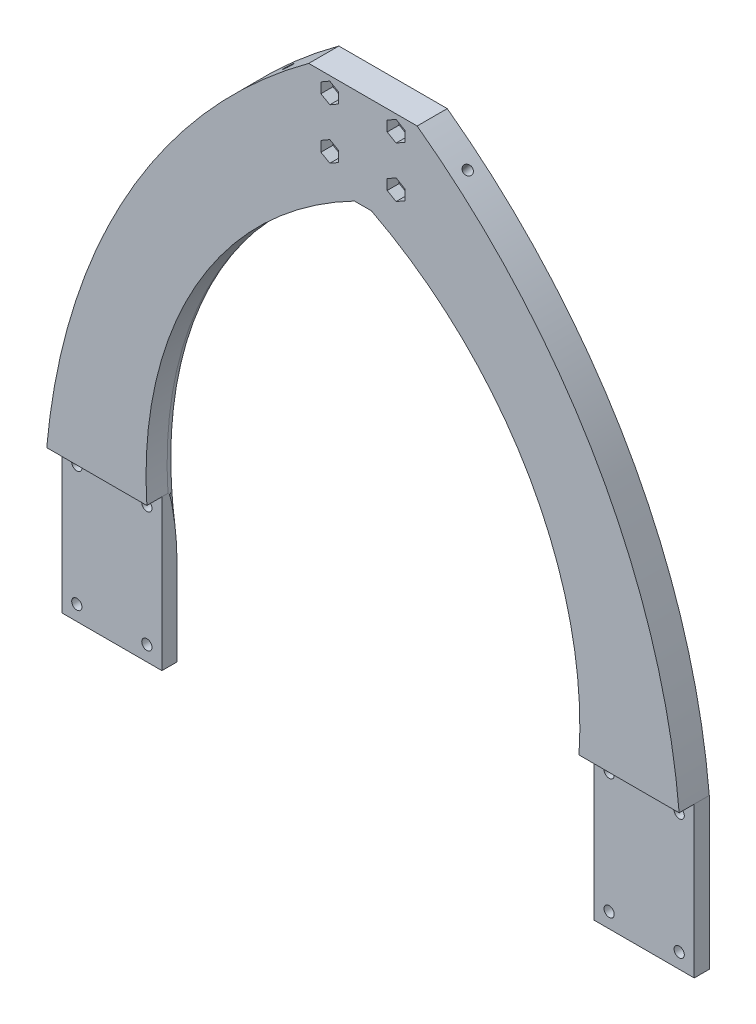
SolidWorks part; units mm, degrees
ref_plane "Ebene vorne" through (0, 0, 0) normal (0, 0, 1) x (1, 0, 0)
ref_plane "Ebene oben" through (0, 0, 0) normal (0, 1, 0) x (1, 0, 0)
ref_plane "Ebene rechts" through (0, 0, 0) normal (1, 0, 0) x (0, 0, -1)
sketch "Skizze1" plane through (0, 0, 0) normal (0, 1, 0) x (1, 0, 0)
  line L1 (-105, -210) -> (105, -210)
  line L2 (-105, -210) -> (-105, 210)
  line L3 (-105, 210) -> (105, 210)
  line L4 (105, -210) -> (105, 210)
  line L5 (-105, -210) -> (105, 210) construction
  line L6 (-105, 210) -> (105, -210) construction
  point P0 (0, 0)
  dimension "D1" = 210
  dimension "D2" = 420
extrude "Aufsatz-Linear austragen1" add sketch "Skizze1" along normal blind 10
ref_plane "Ebene1" through (0, -97.5366, 81.8429) normal (0, -0.766, 0.6428) x (1, 0, 0)
sketch "Skizze2" plane through (0, -97.5366, 81.8429) normal (0, -0.766, 0.6428) x (1, 0, 0)
  line L1 (-105, 167.2972) -> (105, 167.2972) construction
  circle A0 centre (0, 147.2972) radius 5
  dimension "D1" = 10
  dimension "D2" = 20
extrude "Schnitt-Linear austragen1" [suppressed] cut sketch "Skizze2" against normal blind 30 and the other way blind 10
sketch "Skizze3" [suppressed] plane through (0, -67.9923, 57.0523) normal (0, -0.766, 0.6428) x (1, 0, 0)
  circle A0 centre (0, 101.3345) radius 5
  dimension "D1" = 10
extrude "Aufsatz-Linear austragen2" [suppressed] add sketch "Skizze3" along normal blind 0.1
sketch "Skizze4" plane through (0, -97.5366, 81.8429) normal (0, -0.766, 0.6428) x (1, 0, 0)
  line L0 (0, 167.2972) -> (0, 159.9002) construction
  line L1 (-105, 167.2972) -> (105, 167.2972) construction
  line L2 (-25, 167.2972) -> (-25, 202.2972)
  line L3 (-25, 202.2972) -> (25, 202.2972)
  line L4 (-25, 167.2972) -> (25, 167.2972)
  line L5 (25, 167.2972) -> (25, 202.2972)
  point P10 (0, 202.2972)
  dimension "D1" = 50
  dimension "D2" = 35
extrude "Aufsatz-Linear austragen3" [suppressed] add sketch "Skizze4" against normal blind 10 separate body
sketch "Skizze5" plane through (0, 10, 0) normal (0, 1, 0) x (1, 0, 0)
  line L0 (0, 0) -> (0, -210) construction
  line L1 (-105, -210) -> (105, -210) construction
  line L2 (105, -210) -> (18, -210)
  line L3 (-18, -210) -> (-105, -56)
  line L4 (-105, 210) -> (-105, -210) construction
  line L5 (-105, -56) -> (-105, -210)
  line L6 (-105, -210) -> (-18, -210)
  line L7 (105, -56) -> (105, -210)
  line L8 (18, -210) -> (105, -56)
  line L9 (-105, 210) -> (-105, 125)
  line L10 (-105, 125) -> (105, 125)
  line L11 (105, -210) -> (105, 210) construction
  line L12 (105, 125) -> (105, 210)
  line L13 (105, 210) -> (-105, 210)
  line L14 (71.7468, -56) -> (-71.7468, -56)
  line L15 (-71.7468, -56) -> (-2.8247, -178)
  line L16 (71.7468, -56) -> (2.8247, -178)
  line L17 (-2.8247, -178) -> (2.8247, -178)
  line L18 (2.8247, -178) -> (0, -183) construction
  line L19 (-2.8247, -178) -> (0, -183) construction
  point P27 (0, -56)
  dimension "D1" = 36
  dimension "D2" = 154
  dimension "D3" = 85
  dimension "D4" = 32
  dimension "D5" = 27
extrude "Schnitt-Linear austragen2" cut sketch "Skizze5" against normal blind 10
sketch "Skizze6" plane through (0, 10, 0) normal (0, 1, 0) x (1, 0, 0)
  line L0 (0, -210) -> (0, -178) construction
  line L1 (-18, -210) -> (18, -210) construction
  line L2 (-2.8247, -178) -> (2.8247, -178) construction
  line L3 (0, -196.59) -> (-21.075, -196.59) construction
  circle A0 centre (-11, -205) radius 1.7
  circle A1 centre (-11, -188.18) radius 1.7
  circle A2 centre (11, -205) radius 1.7
  circle A3 centre (11, -188.18) radius 1.7
  dimension "D1" = 3.4
  dimension "D2" = 11
  dimension "D3" = 5
  dimension "D4" = 13.41
extrude "Schnitt-Linear austragen3" cut sketch "Skizze6" against normal through all
sketch "Skizze7" plane through (0, 0, 0) normal (0, -1, 0) x (1, 0, 0)
  line L0 (-11, 205) -> (-11, 210) construction
  line L1 (-18, 210) -> (18, 210) construction
  line L2 (-11, 205) -> (-5.1092, 205) construction
  line L3 (-11, 208.4064) -> (-8.05, 206.7032)
  line L4 (-8.05, 206.7032) -> (-8.05, 203.2968)
  line L5 (-11, 201.5936) -> (-8.05, 203.2968)
  line L6 (-11, 201.5936) -> (-13.95, 203.2968)
  line L7 (-13.95, 206.7032) -> (-13.95, 203.2968)
  line L8 (-11, 208.4064) -> (-13.95, 206.7032)
  line L9 (0, 210) -> (0, 121.6034) construction
  line L10 (11, 205) -> (11, 188.18) construction
  line L11 (11, 196.59) -> (0, 196.59) construction
  line L12 (11, 208.4064) -> (8.05, 206.7032)
  line L13 (11, 201.5936) -> (8.05, 203.2968)
  line L14 (8.05, 206.7032) -> (8.05, 203.2968)
  line L15 (11, 201.5936) -> (13.95, 203.2968)
  line L16 (13.95, 206.7032) -> (13.95, 203.2968)
  line L17 (11, 208.4064) -> (13.95, 206.7032)
  line L18 (-8.05, 186.4768) -> (-8.05, 189.8832)
  line L19 (-11, 191.5864) -> (-13.95, 189.8832)
  line L20 (-11, 191.5864) -> (-8.05, 189.8832)
  line L21 (-13.95, 186.4768) -> (-13.95, 189.8832)
  line L22 (-11, 184.7736) -> (-13.95, 186.4768)
  line L23 (-11, 184.7736) -> (-8.05, 186.4768)
  line L24 (8.05, 186.4768) -> (8.05, 189.8832)
  line L25 (11, 191.5864) -> (8.05, 189.8832)
  line L26 (11, 191.5864) -> (13.95, 189.8832)
  line L27 (13.95, 186.4768) -> (13.95, 189.8832)
  line L28 (11, 184.7736) -> (13.95, 186.4768)
  line L29 (11, 184.7736) -> (8.05, 186.4768)
  point P10 (-8.05, 205)
  dimension "D1" = 120
  dimension "D2" = 5.9
extrude "Schnitt-Linear austragen4" cut sketch "Skizze7" against normal blind 4
sketch "Skizze8" plane through (0, 10, 0) normal (0, 1, 0) x (1, 0, 0)
  line L0 (105, 115.41) -> (78.872, 115.41) construction
  line L1 (105, -56) -> (105, 125) construction
  line L2 (-105, 125) -> (105, 125) construction
  dimension "D1" = 9.59
ref_plane "Ebene2" through (0, 62.6966, -52.6087) normal (0, 0.766, -0.6428) x (-1, 0, 0)
sketch "Skizze9" plane through (0, 62.6966, -52.6087) normal (0, 0.766, -0.6428) x (-1, 0, 0)
  line L0 (-105, -81.9813) -> (-78.872, -81.9813) construction
  line L1 (-105, 49.3264) -> (-105, -89.3277) construction
  line L2 (0, -45.2589) -> (0, -16.2619) construction
  circle A0 centre (-100, -81.9813) radius 1.7
  circle A1 centre (100, -81.9813) radius 1.7
  circle A2 centre (-30, -81.9813) radius 1.7
  circle A3 centre (30, -81.9813) radius 1.7
  dimension "D1" = 3.4
  dimension "D2" = 5
  dimension "D3" = 30
extrude "Schnitt-Linear austragen5" [suppressed] cut sketch "Skizze9" against normal through all and the other way through all
ref_plane "Ebene3" through (0, 55.0361, -46.1808) normal (0, 0.766, -0.6428) x (-1, 0, 0)
sketch "Skizze10" [suppressed] plane through (0, 55.0361, -46.1808) normal (0, 0.766, -0.6428) x (-1, 0, 0)
  line L0 (-95, -81.9813) -> (-100, -81.9813) construction
  line L1 (-95, -81.9813) -> (-95, -30.0694) construction
  line L2 (-95, -78.7482) -> (-97.8, -80.3647)
  line L3 (-97.8, -80.3647) -> (-97.8, -83.5979)
  line L4 (-95, -85.2145) -> (-97.8, -83.5979)
  line L5 (-95, -85.2145) -> (-92.2, -83.5979)
  line L6 (-92.2, -80.3647) -> (-92.2, -83.5979)
  line L7 (-95, -78.7482) -> (-92.2, -80.3647)
  line L8 (0, 0) -> (0, -45.6283) construction
  line L9 (-30, -81.9813) -> (-95, -81.9813) construction
  line L10 (-62.5, -81.9813) -> (-62.5, -23.1343) construction
  line L11 (-32.8, -80.3647) -> (-32.8, -83.5979)
  line L12 (-30, -85.2145) -> (-32.8, -83.5979)
  line L13 (-30, -85.2145) -> (-27.2, -83.5979)
  line L14 (-27.2, -80.3647) -> (-27.2, -83.5979)
  line L15 (-30, -78.7482) -> (-27.2, -80.3647)
  line L16 (-30, -78.7482) -> (-32.8, -80.3647)
  line L17 (95, -78.7482) -> (92.2, -80.3647)
  line L18 (92.2, -80.3647) -> (92.2, -83.5979)
  line L19 (95, -85.2145) -> (92.2, -83.5979)
  line L20 (95, -85.2145) -> (97.8, -83.5979)
  line L21 (97.8, -80.3647) -> (97.8, -83.5979)
  line L22 (95, -78.7482) -> (97.8, -80.3647)
  line L23 (30, -78.7482) -> (32.8, -80.3647)
  line L24 (30, -78.7482) -> (27.2, -80.3647)
  line L25 (27.2, -80.3647) -> (27.2, -83.5979)
  line L26 (30, -85.2145) -> (27.2, -83.5979)
  line L27 (30, -85.2145) -> (32.8, -83.5979)
  line L28 (32.8, -80.3647) -> (32.8, -83.5979)
  point P9 (-97.8, -81.9813)
  point P31 (97.8, -81.9813)
  dimension "D1" = 120
  dimension "D2" = 5.6
extrude "Schnitt-Linear austragen6" [suppressed] cut sketch "Skizze10" against normal blind 10 and the other way blind 5
sketch "Skizze13" plane through (0, 10, 0) normal (0, 1, 0) x (1, 0, 0)
  line L0 (71.7468, -56) -> (105, -56) construction
  line L1 (71.7468, -56) -> (96.9548, -70.2409) construction
  line L2 (105, -56) -> (18, -210) construction
  line L3 (0, 0) -> (0, -38.1435) construction
  line L4 (2.8247, -178) -> (71.7468, -56) construction
  line L5 (84.3508, -63.1205) -> (108.762, -19.9098) construction
  line L6 (105, -56) -> (105, 125) construction
  line L7 (88.3734, -56) -> (88.3734, -1) construction
  line L8 (99, -58.9512) -> (105.7595, -46.9862) construction
  line L9 (87.7845, -86.4734) -> (62.5765, -72.2325) construction
  line L10 (77.1638, -80.4734) -> (91.1741, -80.4734) construction
  circle A0 centre (99, -58.9512) radius 1.7
  circle A1 centre (76.9708, -58.9512) radius 1.7
  circle A2 centre (86.8414, -80.4734) radius 1.7
  circle A3 centre (-86.8414, -80.4734) radius 1.7
  circle A4 centre (-99, -58.9512) radius 1.7
  circle A5 centre (-76.9708, -58.9512) radius 1.7
  dimension "D1" = 6
  dimension "D5" = 35
  dimension "D3" = 3.4
  dimension "D6" = 3.4
  dimension "D2" = 6
  dimension "D4" = 6
extrude "Schnitt-Linear austragen7" [suppressed] cut sketch "Skizze13" against normal through all
sketch "Skizze14" plane through (103.579, 0, 58.5154) normal (0.8707, 0, 0.4919) x (0.4919, 0, -0.8707)
  line L0 (-32.111, 5) -> (-32.111, 10)
  line L5 (2.889, 0) -> (2.889, 10) construction
  line L6 (-32.111, 5) -> (2.889, 5)
  line L7 (2.889, 10) -> (-173.9866, 10) construction
  line L8 (-32.111, 10) -> (2.889, 10)
  line L9 (2.889, 10) -> (2.889, 5)
  dimension "D1" = 35
extrude "Schnitt-Linear austragen8" [suppressed] cut sketch "Skizze14" against normal up to surface (28.9525 mm away)
mirror "Spiegeln1" [suppressed] about plane through (0, 0, 0) normal (1, 0, 0)
sketch "Skizze15" [suppressed] plane through (95, 0, 0) normal (1, 0, 0) x (0, 0, -1)
  line L0 (4, 10) -> (4, 0)
  line L1 (4, 0) -> (65, 0)
  line L2 (65, 0) -> (65, 10)
  line L3 (65, 10) -> (4, 10)
extrude "Schnitt-Linear austragen9" [suppressed] cut sketch "Skizze15" against normal through all
sketch "Skizze16" plane through (0, 0, 0) normal (0, -1, 0) x (1, 0, 0)
  line L0 (0, 210) -> (0, 178) construction
  line L1 (-18, 210) -> (18, 210) construction
  line L2 (-2.8247, 178) -> (2.8247, 178) construction
  line L3 (11, 196.59) -> (0, 196.59) construction
  line L4 (11, 205) -> (11, 188.18) construction
  line L6 (-17.5, 193.09) -> (17.5, 193.09)
  line L7 (-17.5, 193.09) -> (-17.5, 200.09)
  line L8 (-17.5, 200.09) -> (17.5, 200.09)
  line L9 (17.5, 193.09) -> (17.5, 200.09)
  line L10 (-17.5, 193.09) -> (17.5, 200.09) construction
  line L11 (-17.5, 200.09) -> (17.5, 193.09) construction
  dimension "D1" = 7
  dimension "D2" = 35
extrude "Schnitt-Linear austragen10" [suppressed] cut sketch "Skizze16" against normal blind 5
sketch "Skizze17" [suppressed] plane through (17.5, 0, 0) normal (-1, 0, 0) x (0, 0, 1)
  line L0 (196.59, 0) -> (196.59, 11.1261) construction
  line L1 (193.09, 0) -> (200.09, 0) construction
  line L2 (193.09, 5) -> (196.59, 8.5)
  line L3 (196.59, 8.5) -> (200.09, 5)
  line L4 (200.09, 5) -> (193.09, 5)
  dimension "D1" = 90
extrude "Schnitt-Linear austragen11" [suppressed] cut sketch "Skizze17" along normal up to surface (35 mm away)
sketch "Skizze18" [suppressed] plane through (0, 10, 0) normal (0, 1, 0) x (1, 0, 0)
  line L0 (0, -210) -> (0, 0) construction
  line L1 (-18, -210) -> (18, -210) construction
  line L2 (62.5765, -72.2325) -> (35.4483, -67.5372)
  line L3 (15.3378, -155.8503) -> (-22.1774, -134.6566)
  line L4 (2.8247, -178) -> (62.5765, -72.2325) construction
  line L5 (-15.3378, -155.8503) -> (22.1774, -134.6566)
  line L6 (58.6594, -79.166) -> (40.7308, -76.063)
  line L7 (0, -147.1854) -> (19.5429, -147.1854) construction
  line L8 (0, -95.4) -> (31.4297, -95.4) construction
  line L9 (11.6488, -162.3803) -> (0, -155.7995)
  line L10 (-71.7468, -56) -> (-2.8247, -178) construction
  line L11 (0, -95.4) -> (-37.5153, -116.5937) construction
  line L12 (-37.5153, -116.5937) -> (-39.2566, -117.5774) construction
  line L13 (-11.6488, -162.3803) -> (0, -155.7995)
  line L14 (-58.6594, -79.166) -> (-40.7308, -76.063)
  line L15 (-62.5765, -72.2325) -> (-35.4483, -67.5372)
  circle A0 centre (0, -95.4) radius 33.5
  arc A1 (7.4594, -151.3994) -> (7.4594, -142.9713) centre (9.84, -147.1854) cw
  arc A2 (-7.4594, -151.3994) -> (-7.4594, -142.9713) centre (-9.84, -147.1854) ccw
  circle A3 centre (0, -95.4) radius 45.0879
  point P17 (0, -147.1854)
  point P36 (5, -147.1854)
  point P40 (-5, -147.1854)
  line M16 (62.5765, -72.2325) -> (2.8247, -178)
  line M18 (-2.8247, -178) -> (-71.7468, -56)
  dimension "D2" = 67
  dimension "D5" = 2
  dimension "D4" = 10
  dimension "D1" = 114.6
  dimension "D3" = 7.5
  dimension "D6" = 7.5
extrude "Aufsatz-Linear austragen4" [suppressed] add sketch "Skizze18" against normal blind 10 contours A3 L15 L14 M18 | A3 A0 M16 M18 | A3 L6 L2 M16 | A2 L5 L3 | A3 L3 L5 | L3 A1 L5 | L13 L9 L3 L5 M18 M16
sketch "Skizze19" [suppressed] plane through (0, 0, 0) normal (0, -1, 0) x (1, 0, 0)
  circle A0 centre (0, 35.4) radius 31.5
  circle A1 centre (0, 35.4) radius 33.5
  circle A2 centre (0, 35.4) radius 33.5 construction
  dimension "D1" = 63
extrude "Aufsatz-Linear austragen5" [suppressed] add sketch "Skizze19" against normal blind 1
sketch "Skizze20" plane through (0, 10, 0) normal (0, 1, 0) x (1, 0, 0)
  line L0 (105, 119.52) -> (55.4083, 119.52) construction
  line L1 (105, -56) -> (105, 125) construction
  line L2 (-105, 125) -> (105, 125) construction
  line L3 (0, 125) -> (0, 96.9732) construction
  line L4 (105, 43.82) -> (35.5869, 43.82) construction
  circle A0 centre (96, 119.52) radius 1.7
  circle A1 centre (54, 119.52) radius 1.7
  circle A2 centre (-54, 119.52) radius 1.7
  circle A3 centre (-96, 119.52) radius 1.7
  circle A4 centre (92.5, 43.82) radius 1.7
  circle A5 centre (57.5, 43.82) radius 1.7
  circle A6 centre (-92.5, 43.82) radius 1.7
  circle A7 centre (-57.5, 43.82) radius 1.7
  dimension "D1" = 3.4
  dimension "D2" = 5.48
  dimension "D3" = 9
  dimension "D4" = 42
  dimension "D5" = 75.7
  dimension "D6" = 12.5
  dimension "D7" = 35
extrude "Schnitt-Linear austragen12" cut sketch "Skizze20" against normal through all
sketch "Skizze21" plane through (0, 10, 0) normal (0, 1, 0) x (1, 0, 0)
  line L0 (-71.7468, -56) -> (-71.7468, 19)
  line L1 (-71.7468, 19) -> (71.7468, 19)
  line L2 (71.7468, 19) -> (71.7468, -56)
  line L3 (71.7468, -56) -> (-71.7468, -56) construction
  line L4 (-71.7468, -56) -> (71.7468, -56)
  dimension "D1" = 75
extrude "Schnitt-Linear austragen13" cut sketch "Skizze21" against normal through all
sketch "Skizze22" plane through (0, 10, 0) normal (0, 1, 0) x (1, 0, 0)
  line L0 (-71.7468, -56) -> (-2.8247, -178)
  arc A0 (-71.7468, -56) -> (-2.8247, -178) centre (55.7113, -64.4627) ccw
  line M19 (-2.8247, -178) -> (-71.7468, -56)
extrude "Schnitt-Linear austragen14" cut sketch "Skizze22" against normal through all contours M19 region at (-44.6278, 10, 121.1478)
sketch "Skizze23" plane through (0, 10, 0) normal (0, 1, 0) x (1, 0, 0)
  line L0 (-18, -210) -> (-105, -56) construction
  line L1 (-105, -56) -> (-18, -210)
  arc A0 (-18, -210) -> (-105, -56) centre (108.9155, -36.7263) cw
  arc A2 (-71.7468, -56) -> (-2.8247, -178) centre (55.7113, -64.4627) ccw construction
  dimension "D1" = 60
extrude "Aufsatz-Linear austragen6" add sketch "Skizze23" against normal blind 10
mirror "Spiegeln2" about plane through (0, 0, 0) normal (1, 0, 0) of "Aufsatz-Linear austragen6", "Schnitt-Linear austragen14"
sketch "Skizze25" plane through (0, 10, 0) normal (0, 1, 0) x (1, 0, 0)
  line L0 (-105, -56) -> (-71.7468, -56) construction
  line L1 (-105, -6) -> (-105, -56) construction
  line L2 (-105, -6) -> (-71.7468, -6) construction
  line L3 (-71.7468, 19) -> (-71.7468, -56) construction
  line L4 (-88.3734, -6) -> (-88.3734, -56) construction
  line L5 (-105, -31) -> (-71.7468, -31) construction
  line L6 (-105, 125) -> (-105, -56) construction
  circle A0 centre (-100, -11) radius 1.7
  circle A1 centre (-76.7468, -11) radius 1.7
  circle A2 centre (-76.7468, -51) radius 1.7
  circle A3 centre (-100, -51) radius 1.7
  dimension "D2" = 3.4
  dimension "D1" = 50
  dimension "D3" = 5
  dimension "D4" = 5
extrude "Schnitt-Linear austragen15" cut sketch "Skizze25" against normal through all
sketch "Skizze26" plane through (-105, 0, 0) normal (-1, 0, 0) x (0, 0, 1)
  line L0 (56, 5) -> (56, 0)
  line L1 (56, 0) -> (56, 10) construction
  line L2 (56, 5) -> (6, 5)
  line L3 (6, 5) -> (6, 10)
  line L4 (-125, 0) -> (56, 0) construction
  line L5 (5.0128, 19.5087) -> (6, 10)
  line L6 (5.0128, 19.5087) -> (-137.7077, 19.5087)
  line L7 (-137.7077, 19.5087) -> (-137.7077, -14.4017)
  line L8 (-137.7077, -14.4017) -> (4.1968, -14.4017)
  line L9 (4.1968, -14.4017) -> (56, 0)
  line L10 (-125, 10) -> (56, 10) construction
mirror "Spiegeln3" about plane through (0, 0, 0) normal (1, 0, 0) of "Schnitt-Linear austragen15"
extrude "Schnitt-Linear austragen16" cut sketch "Skizze26" against normal through all
fillet "Verrundung1" radius 3 3 edges at (55.5067, 10, 127.2937) (-55.5067, 10, 127.2937) (0, 10, 178)
sketch "Skizze27" plane through (0, 0, 0) normal (0, -1, 0) x (1, 0, 0)
  line L0 (18, 210) -> (40.9051, 190.6259) construction
  arc A0 (105, 56) -> (18, 210) centre (-108.9155, 36.7263) ccw construction
  dimension "D1" = 30
ref_plane "Ebene4" through (111.0524, 0, 131.2926) normal (0.6458, 0, 0.7635) x (0.7635, 0, -0.6458)
sketch "Skizze28" plane through (111.0524, 0, 131.2926) normal (0.6458, 0, 0.7635) x (0.7635, 0, -0.6458)
  line L0 (-106.8754, 0) -> (-106.8754, 10) construction
  line L1 (-121.8754, 0) -> (-91.8754, 0) construction
  line L2 (44.003, 10) -> (-121.8754, 10) construction
  circle A0 centre (-106.8754, 5) radius 1.5
  dimension "D1" = 3
extrude "Schnitt-Linear austragen17" cut sketch "Skizze28" against normal blind 8 and the other way blind 10
mirror "Spiegeln4" about plane through (0, 0, 0) normal (1, 0, 0) of "Schnitt-Linear austragen17"
move or copy body "Körper-Verschieben/Kopieren1" bodies to move or copy 127 copy no rotation origin (0, 5.338, 108) rotation axis (-1, 0, 0) rotation angle 90
